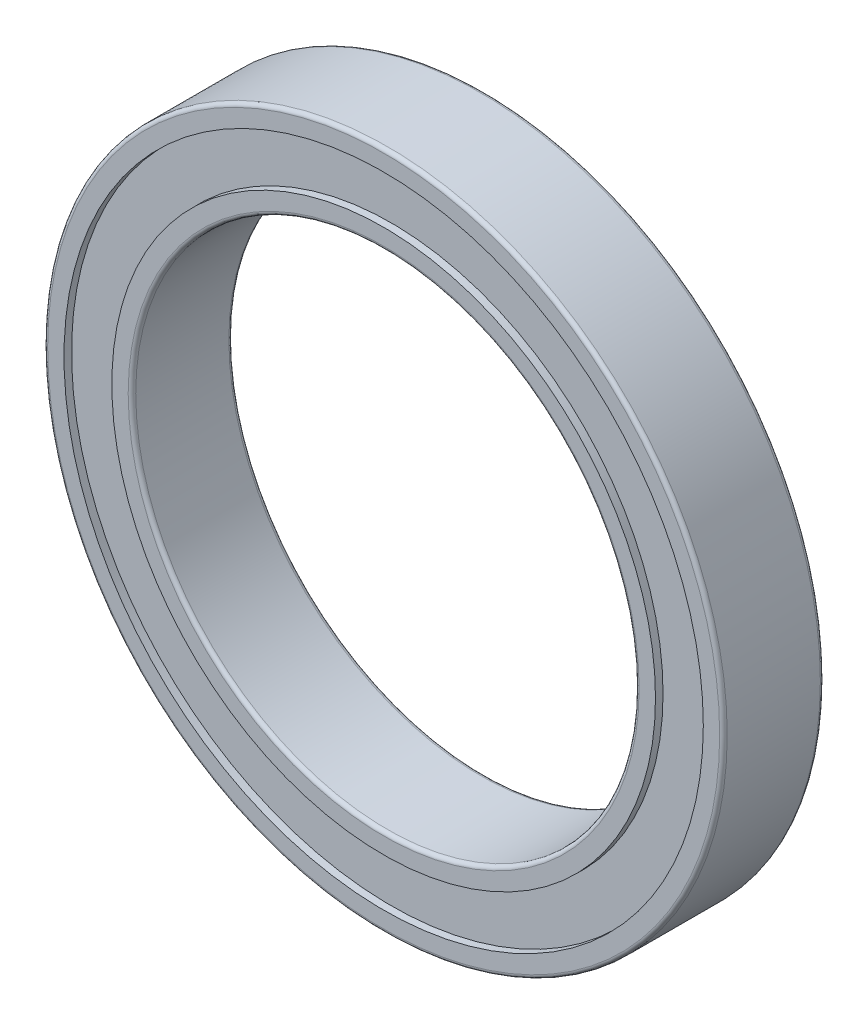
SolidWorks part; units mm, degrees
ref_plane "Front Plane" through (0, 0, 0) normal (0, 0, 1) x (1, 0, 0)
ref_plane "Top Plane" through (0, 0, 0) normal (0, 1, 0) x (1, 0, 0)
ref_plane "Right Plane" through (0, 0, 0) normal (1, 0, 0) x (0, 0, -1)
sketch "Sketch1" plane through (0, 0, 0) normal (0, 0, 1) x (1, 0, 0)
  circle A0 centre (0, 0) radius 10
  circle A1 centre (0, 0) radius 13.5
  dimension "D1" = 20
  dimension "D2" = 27
extrude "Boss-Extrude1" add sketch "Sketch1" along normal blind 4
sketch "Sketch2" plane through (0, 0, 4) normal (0, 0, 1) x (1, 0, 0)
  circle A3 centre (0, 0) radius 12.7
  circle A6 centre (0, 0) radius 10.8
  dimension "D1" = 21.6
  dimension "D2" = 25.4
extrude "Cut-Extrude1" cut sketch "Sketch2" against normal blind 0.3
extrude "Cut-Extrude2" cut sketch "Sketch2<2>" along normal blind 0.5 from surface starting at face at (13.5, 0, 0)
sketch "Sketch2<2>" plane through (0, 0, 4) normal (0, 0, 1) x (1, 0, 0) same geometry as "Sketch2"
fillet "Fillet1" radius 0.15 4 edges at (10, 0, 4) (13.5, 0, 4) (10, 0, 0) (13.5, 0, 0)
